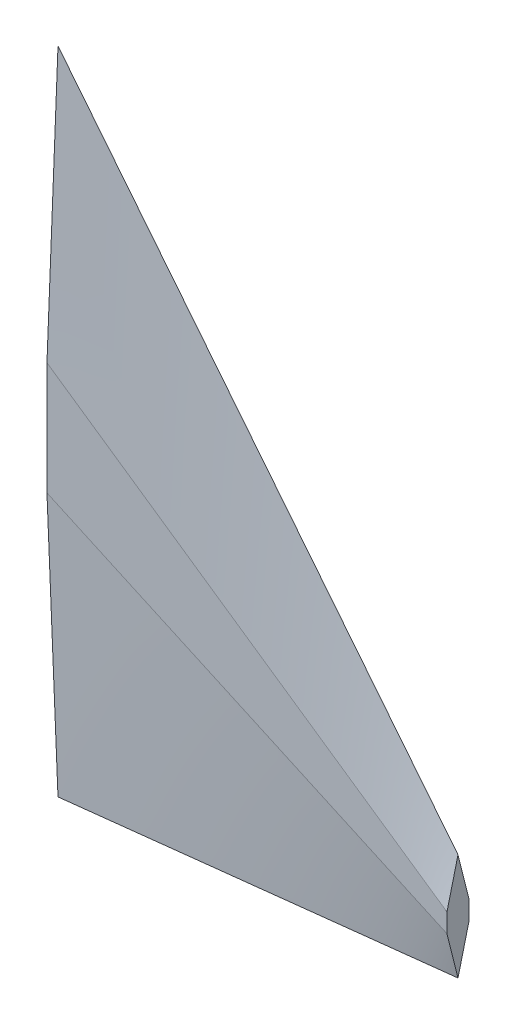
SolidWorks part; units mm, degrees
material "Hexcel AS4C (3000 Filaments)"
ref_plane "Front Plane" through (0, 0, 0) normal (0, 0, 1) x (1, 0, 0)
ref_plane "Top Plane" through (0, 0, 0) normal (0, 1, 0) x (1, 0, 0)
ref_plane "Right Plane" through (0, 0, 0) normal (1, 0, 0) x (0, 0, -1)
sketch "Sketch1" plane through (0, 0, 0) normal (1, 0, 0) x (0, 0, -1)
  line L0 (0, 74.29) -> (2.5212, 12.87)
  line L1 (2.5212, 12.87) -> (2.5212, -12.87)
  line L2 (2.5212, -12.87) -> (0, -74.29)
  line L3 (0, 10.685) -> (0, 13.7664) construction
  line L4 (0, 74.29) -> (0, -74.29) construction
  line L5 (-2.5212, -12.87) -> (0, -74.29)
  line L6 (-2.5212, 12.87) -> (-2.5212, -12.87)
  line L7 (0, 74.29) -> (-2.5212, 12.87)
  point P4 (2.5212, 0)
  point P7 (0, 0)
  dimension "D1" = 25.74
  dimension "D2" = 148.58
ref_plane "Plane1" through (91.39, 0, 0) normal (1, 0, 0) x (0, 0, -1)
sketch "Sketch2" plane through (91.39, 0, 0) normal (1, 0, 0) x (0, 0, -1)
  line L2 (0, -40.04) -> (0, -64.424) construction
  line L8 (0, -64.424) -> (2.5212, -54.391)
  line L9 (0, -199989.315) -> (0, 200013.7664) construction
  line L10 (2.5212, 12.87) -> (2.5212, -12.87) construction
  line L11 (2.5212, -54.391) -> (2.5212, -50.073)
  line L12 (2.5212, -50.073) -> (0, -40.04)
  line L13 (-2.5212, -50.073) -> (0, -40.04)
  line L14 (-2.5212, -54.391) -> (-2.5212, -50.073)
  line L15 (0, -64.424) -> (-2.5212, -54.391)
  point P8 (0, -52.232)
  point P9 (2.5212, -52.232)
  dimension "D1" = 24.384
  dimension "D2" = 4.318
  dimension "D3" = 114.33
loft "Loft1" add profiles "Sketch1", "Sketch2" connector at (0, 12.87, -2.5212) connector at (91.39, -50.073, -2.5212)
ref_plane "Plane2" through (0, -74.422, 0) normal (0, 1, 0) x (1, 0, 0)
